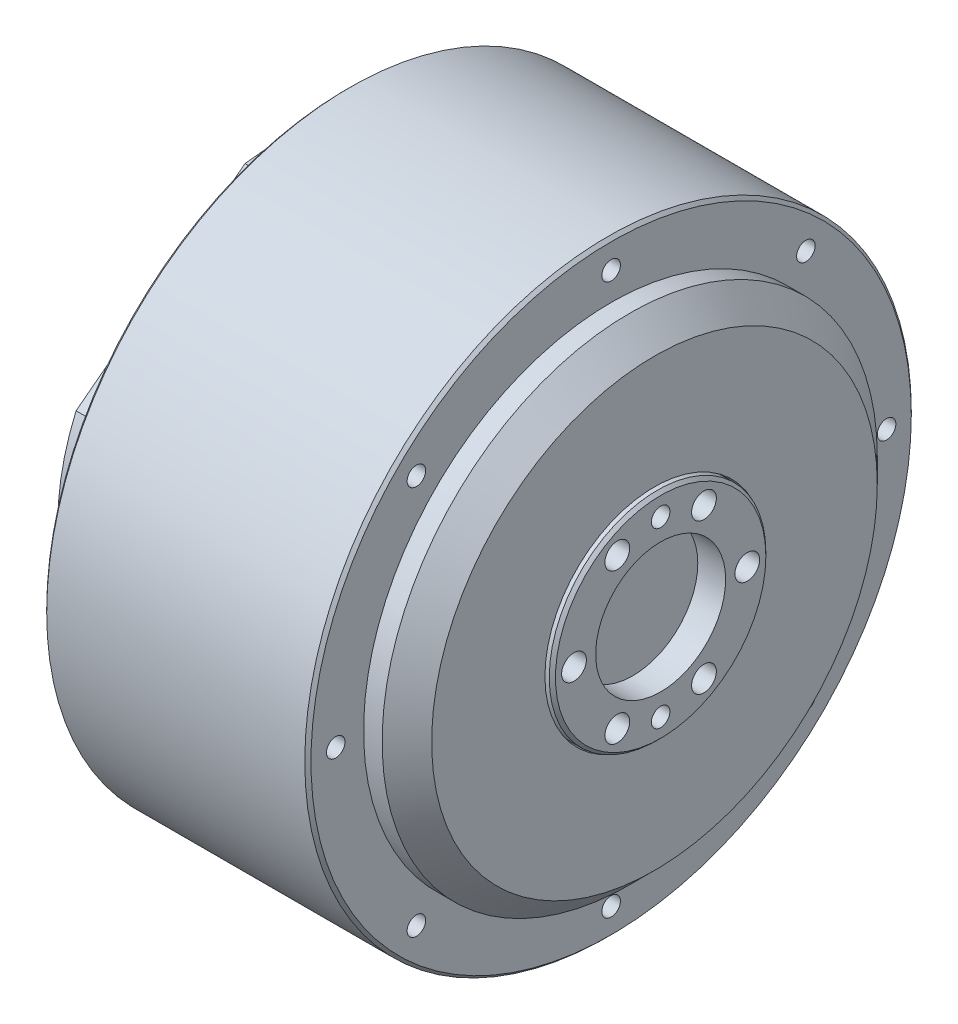
SolidWorks part; units mm, degrees
material "Magnesium Alloy"
ref_plane "Front Plane" through (0, 0, 0) normal (0, 0, 1) x (1, 0, 0)
ref_plane "Top Plane" through (0, 0, 0) normal (0, 1, 0) x (1, 0, 0)
ref_plane "Right Plane" through (0, 0, 0) normal (1, 0, 0) x (0, 0, -1)
sketch "Sketch1" plane through (0, 0, 0) normal (0, 0, 1) x (1, 0, 0)
  line L0 (-50.7, 49) -> (-50.7, 0)
  line L1 (-50.7, 0) -> (-8, 0)
  line L2 (-8, 0) -> (-8, 49)
  line L3 (-8, 49) -> (-50.7, 49)
  line L4 (-50.7, 0) -> (-8, 0) construction
revolve "Revolve1" add sketch "Sketch1" angle 360 about L4 reverse direction yes
sketch "Sketch2" plane through (-50.7, 0, 0) normal (-1, 0, 0) x (0, 0, 1)
  circle A0 centre (0, 0) radius 35.5
extrude "Boss-Extrude1" add sketch "Sketch2" along normal blind 11.2
sketch "Sketch3" plane through (-61.9, 0, 0) normal (-1, 0, 0) x (0, 0, 1)
  line L0 (5.253, 35.1092) -> (32.5533, 14.161)
  arc A0 (32.5533, 14.161) -> (5.253, 35.1092) centre (0, 0) ccw
extrude "Cut-Extrude1" cut sketch "Sketch3" against normal blind 8
sketch "Sketch4" plane through (-8, 0, 0) normal (1, 0, 0) x (0, 0, -1)
  circle A0 centre (0, 0) radius 40
extrude "Boss-Extrude2" add sketch "Sketch4" along normal blind 3
sketch "Sketch5" plane through (-5, 0, 0) normal (1, 0, 0) x (0, 0, -1)
  circle A0 centre (0, 0) radius 40
extrude "Boss-Extrude3" add sketch "Sketch5" along normal blind 4 draft 45
hole_wizard "M33 Clearance Hole1" positions "Sketch7" profile "Sketch6" hole size "M33" standard "ANSI Metric"
sketch "Sketch7" plane through (-1, 0, 0) normal (1, 0, 0) x (0, 0, -1)
  point P0 (0, 0)
sketch "Sketch6" plane through (-1, 0, 0) normal (0, 1, 0) x (0, 0, -1)
  line L0 (0, 0) -> (0, 7.5)
  line L1 (0, 7.5) -> (17.7, 7.5)
  line L2 (17.7, 7.5) -> (17.7, 0)
  line L5 (17.7, 0) -> (0, 0)
  line L10 (0, 7.5) -> (-17.7, 7.5) construction
  line L11 (0, -6.35) -> (0, 107.95) construction
  dimension "Hole Dia." = 35.4
  dimension "Hole Depth" = 7.5
  dimension "Drill Angle" = 180
sketch "Sketch8" plane through (0, 0, 0) normal (0, 0, 1) x (1, 0, 0)
  line L0 (-8.5, 17.5) -> (-8.5, 0)
  line L1 (-8.5, 0) -> (0, 0)
  line L2 (0, 0) -> (0, 17.5)
  line L3 (0, 17.5) -> (-8.5, 17.5)
  line L4 (-8.5, 0) -> (0, 0) construction
revolve "Revolve2" add sketch "Sketch8" angle 360 about L4 reverse direction yes
hole_wizard "Ø3.0 (3) Diameter Hole1" positions "Sketch10" profile "Sketch9" hole size "Ø3.0" standard "ANSI Metric"
sketch "Sketch10" plane through (-50.7, 0, 0) normal (-1, 0, 0) x (0, 0, 1)
  point P0 (39.2649, 16.264)
  point P1 (39.2649, -16.264)
  point P2 (16.264, -39.2649)
  point P3 (-16.264, -39.2649)
  point P4 (-39.2649, -16.264)
  point P5 (-39.2649, 16.264)
  point P6 (-16.264, 39.2649)
  point P7 (16.264, 39.2649)
sketch "Sketch9" plane through (-50.7, 16.264, 39.2649) normal (0, 1, 0) x (0, 0, 1)
  line L0 (0, 0) -> (0, 4)
  line L1 (0, 4) -> (1.5, 4)
  line L2 (1.5, 4) -> (1.5, 0)
  line L5 (1.5, 0) -> (0, 0)
  line L10 (0, 4) -> (-1.5, 4) construction
  line L11 (0, -6.35) -> (0, 107.95) construction
  dimension "Hole Dia." = 3
  dimension "Hole Depth" = 4
  dimension "Drill Angle" = 180
hole_wizard "Ø3.0 (3) Diameter Hole2" positions "Sketch12" profile "Sketch11" hole size "Ø3.0" standard "ANSI Metric"
sketch "Sketch12" plane through (-8, 0, 0) normal (1, 0, 0) x (0, 0, -1)
  point P0 (31.4663, 31.4663)
  point P1 (44.5, 0)
  point P2 (31.4663, -31.4663)
  point P3 (0, -44.5)
  point P4 (-31.4663, -31.4663)
  point P5 (-44.5, 0)
  point P6 (-31.4663, 31.4663)
  point P7 (0, 44.5)
sketch "Sketch11" plane through (-8, 31.4663, -31.4663) normal (0, 1, 0) x (0, 0, -1)
  line L0 (0, 0) -> (0, 8)
  line L1 (0, 8) -> (1.5, 8)
  line L2 (1.5, 8) -> (1.5, 0)
  line L5 (1.5, 0) -> (0, 0)
  line L10 (0, 8) -> (-1.5, 8) construction
  line L11 (0, -6.35) -> (0, 107.95) construction
  dimension "Hole Dia." = 3
  dimension "Hole Depth" = 8
  dimension "Drill Angle" = 180
hole_wizard "Ø21.0 (21) Diameter Hole1" positions "Sketch14" profile "Sketch13" hole size "Ø21.0" standard "ANSI Metric"
sketch "Sketch14" plane through (0, 0, 0) normal (1, 0, 0) x (0, 0, -1)
  point P0 (0, 0)
sketch "Sketch13" plane through (0, 0, 0) normal (0, 1, 0) x (0, 0, -1)
  line L0 (0, 0) -> (0, 4.5)
  line L1 (0, 4.5) -> (10.5, 4.5)
  line L2 (10.5, 4.5) -> (10.5, 0)
  line L5 (10.5, 0) -> (0, 0)
  line L10 (0, 4.5) -> (-10.5, 4.5) construction
  line L11 (0, -6.35) -> (0, 107.95) construction
  dimension "Hole Dia." = 21
  dimension "Hole Depth" = 4.5
  dimension "Drill Angle" = 180
hole_wizard "Ø4.0 (4) Diameter Hole1" positions "Sketch16" profile "Sketch15" hole size "Ø4.0" standard "ANSI Metric"
sketch "Sketch16" plane through (0, 0, 0) normal (1, 0, 0) x (0, 0, -1)
  point P0 (-14, 0)
  point P1 (-7, 12.1244)
  point P2 (7, 12.1244)
  point P3 (14, 0)
  point P4 (7, -12.1244)
  point P5 (-7, -12.1244)
sketch "Sketch15" plane through (0, 0, 14) normal (0, 1, 0) x (0, 0, -1)
  line L0 (0, 0) -> (0, 8)
  line L1 (0, 8) -> (2, 8)
  line L2 (2, 8) -> (2, 0)
  line L5 (2, 0) -> (0, 0)
  line L10 (0, 8) -> (-2, 8) construction
  line L11 (0, -6.35) -> (0, 107.95) construction
  dimension "Hole Dia." = 4
  dimension "Hole Depth" = 8
  dimension "Drill Angle" = 180
hole_wizard "Ø3.0 (3) Diameter Hole3" positions "Sketch18" profile "Sketch17" hole size "Ø3.0" standard "ANSI Metric"
sketch "Sketch18" plane through (0, 0, 0) normal (1, 0, 0) x (0, 0, -1)
  point P0 (0, -14)
  point P1 (0, 14)
sketch "Sketch17" plane through (0, -14, 0) normal (0, 1, 0) x (0, 0, -1)
  line L0 (0, 0) -> (0, 3)
  line L1 (0, 3) -> (1.5, 3)
  line L2 (1.5, 3) -> (1.5, 0)
  line L5 (1.5, 0) -> (0, 0)
  line L10 (0, 3) -> (-1.5, 3) construction
  line L11 (0, -6.35) -> (0, 107.95) construction
  dimension "Hole Dia." = 3
  dimension "Hole Depth" = 3
  dimension "Drill Angle" = 180
chamfer "Chamfer1" distance 0.5 angle 45 3 edges at (-50.7, 0, -49) (0, 0, -17.5) (-8, 0, -49)
